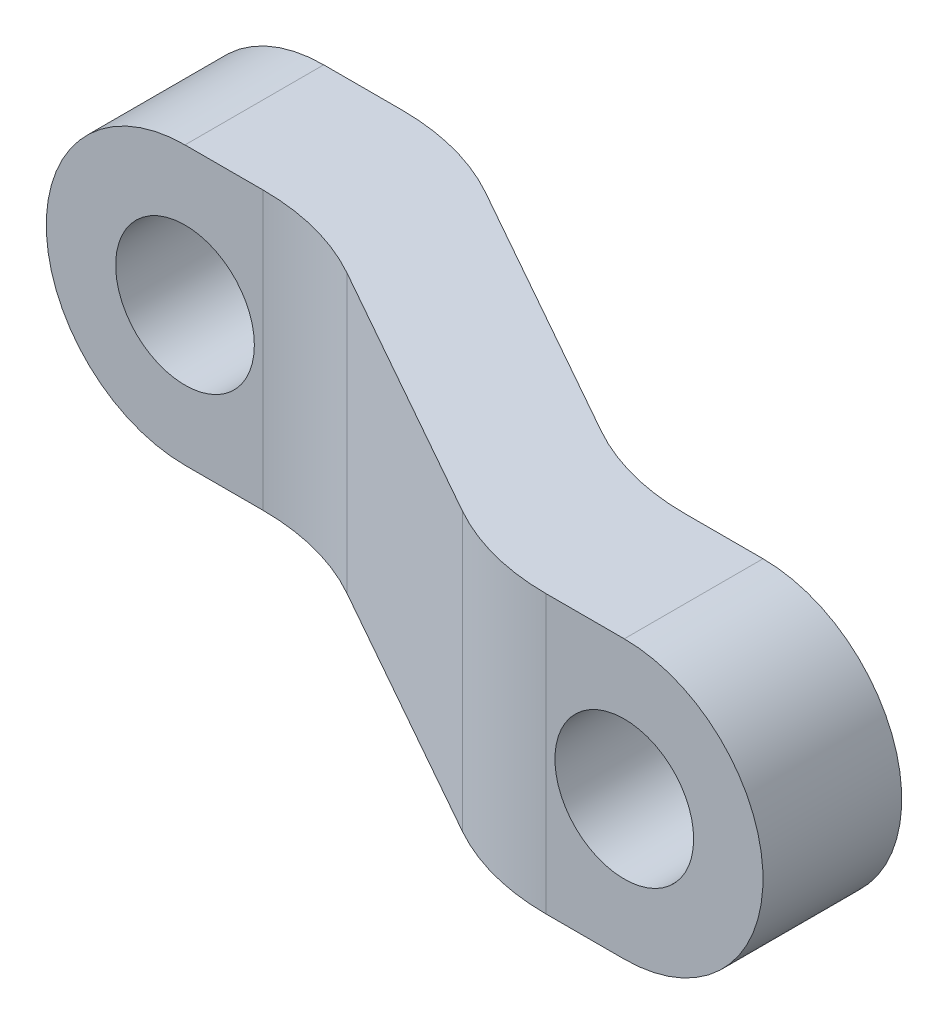
SolidWorks part; units mm, degrees
ref_plane "Front Plane" through (0, 0, 0) normal (0, 0, 1) x (1, 0, 0)
ref_plane "Top Plane" through (0, 0, 0) normal (0, 1, 0) x (1, 0, 0)
ref_plane "Right Plane" through (0, 0, 0) normal (1, 0, 0) x (0, 0, -1)
sketch "Sketch2" plane through (0, 0, 0) normal (0, 0, 1) x (1, 0, 0)
  line L1 (-3, -3) -> (3, -3)
  line L2 (-3, -3) -> (-3, 3)
  line L3 (-3, 3) -> (3, 3)
  line L4 (3, -3) -> (3, 3)
  line L5 (-3, -3) -> (3, 3) construction
  line L6 (-3, 3) -> (3, -3) construction
  circle A0 centre (0, 0) radius 1.5
  circle A1 centre (0, 0) radius 3
  dimension "D1" = 3
  dimension "D2" = 6
  dimension "D3" = 6
sketch "Sketch3" plane through (0, 0, 0) normal (0, 1, 0) x (1, 0, 0)
  line L0 (-1.5, 0) -> (1.5, 0) construction
  line L1 (-6, -1.5) -> (3, -1.5)
  line L2 (-6, -1.5) -> (-6, 1.5)
  line L3 (-6, 1.5) -> (3, 1.5)
  line L4 (3, -1.5) -> (3, 1.5)
  line L5 (-6, -1.5) -> (3, 1.5) construction
  line L6 (-6, 1.5) -> (3, -1.5) construction
  line L7 (-3, 0) -> (3, 0) construction
  line L8 (-3, 0) -> (3, 0) construction
  line L9 (-17, 4.5) -> (-11, 4.5) construction
  line L10 (-17, 3) -> (-8, 3)
  line L11 (-17, 3) -> (-17, 6)
  line L12 (-17, 6) -> (-8, 6)
  line L13 (-8, 3) -> (-8, 6)
  line L14 (-17, 3) -> (-8, 6) construction
  line L15 (-17, 6) -> (-8, 3) construction
  line L16 (-3, 0) -> (-3, -1.5) construction
  line L17 (-11, 4.5) -> (-11, 3) construction
  line L18 (-11, 3) -> (-11, 6) construction
  line L19 (-11, 3) -> (-3, -1.5)
  line L20 (-11, 6) -> (-3, 1.5)
  point P0 (-1.5, 0)
  point P15 (0, 0)
  point P16 (-12.5, 4.5)
  dimension "D1" = 3
  dimension "D2" = 9
  dimension "D3" = 6
  dimension "D4" = 3
  dimension "D5" = 9
  dimension "D6" = 6
  dimension "D7" = 5
  dimension "D8" = 1.5
extrude "Boss-Extrude1" add sketch "Sketch3" along normal blind 3 and the other way blind 3 contours L10 L19 L13 L1 L12 L11 | L13 L19 L1 | L20 L2 L1 L4 L3 | L20 L12 L2 region at (-1.1379, 0, -0.097) region at (-7, 0, -2.25) region at (-12.8621, 0, -4.403)
sketch "Sketch4" plane through (0, 0, -3) normal (0, 0, 1) x (1, 0, 0)
  line L0 (-17, -3) -> (-17, 3) construction
  line L1 (-17, 3) -> (-11, 3) construction
  line L2 (-17, -3) -> (-11, -3) construction
  line L3 (-11, 3) -> (-17, 3)
  line L4 (-11, 3) -> (-11, -3)
  line L5 (-11, -3) -> (-17, -3)
  line L6 (-17, 3) -> (-17, -3)
  line L7 (-11, 3) -> (-17, -3) construction
  line L8 (-11, -3) -> (-17, 3) construction
  circle A0 centre (-14, 0) radius 3
  circle A1 centre (-14, 0) radius 1.5
  line M5 (-17, 3) -> (-17, -3)
  line M6 (-17, -3) -> (-11, -3)
  dimension "D1" = 6
  dimension "D2" = 3
extrude "Cut-Extrude1" cut sketch "Sketch2" against normal blind 3 and the other way blind 3 contours A1 L4 L3 | A1 L1 L4 | A0 region at (2.3299, -2.3299, 0) region at (2.3299, 2.3299, 0) region at (0, 0, 0)
extrude "Cut-Extrude3" cut sketch "Sketch4" against normal blind 3 and the other way blind 3 contours A0 L6 M6 | A0 L3 M5 | A1 region at (-16.3299, 2.3299, -3) region at (-16.3299, -2.3299, -3) region at (-14, 0, -3)
fillet "Fillet1" radius 5 4 edges at (-11, 0, -3) (-3, 0, 1.5) (-3, 0, -1.5) (-11, 0, -6)
